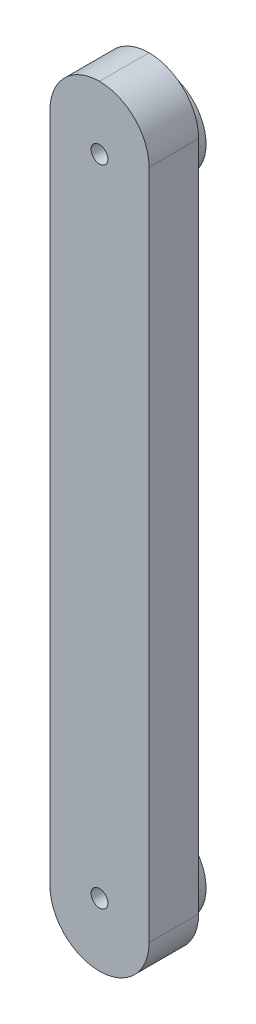
SolidWorks part; units mm, degrees
material "PETG"
ref_plane "Front Plane" through (0, 0, 0) normal (0, 0, 1) x (1, 0, 0)
ref_plane "Top Plane" through (0, 0, 0) normal (0, 1, 0) x (1, 0, 0)
ref_plane "Right Plane" through (0, 0, 0) normal (1, 0, 0) x (0, 0, -1)
sketch "Sketch1" plane through (0, 0, 0) normal (0, 0, 1) x (1, 0, 0)
  line L1 (-10, 77.75) -> (10, 77.75)
  line L2 (-10, 77.75) -> (-10, -77.75)
  line L3 (-10, -77.75) -> (10, -77.75)
  line L4 (10, 77.75) -> (10, -77.75)
  point P8 (-10, 0)
  point P9 (0, 77.75)
  dimension "D1" = 20
  dimension "D2" = 155.5
extrude "Boss-Extrude1" add sketch "Sketch1" along normal blind 10
sketch "Sketch2" plane through (0, 0, 0) normal (0, 0, -1) x (-1, 0, 0)
  line L0 (0, 65) -> (0, -65) construction
  circle A0 centre (0, 65) radius 9
  circle A1 centre (0, -65) radius 9
  dimension "D1" = 130
  dimension "D2" = 18
extrude "Boss-Extrude2" add sketch "Sketch2" along normal blind 2.5
fillet "Fillet1" radius 10 4 edges at (10, -77.75, 5) (-10, -77.75, 5) (-10, 77.75, 5) (10, 77.75, 5)
sketch "Sketch3" plane through (0, 0, -2.5) normal (0, 0, -1) x (-1, 0, 0)
  circle A0 centre (0, 65) radius 1.7
  circle A1 centre (0, -65) radius 1.7
  dimension "D1" = 3.4
extrude "Cut-Extrude1" cut sketch "Sketch3" against normal through all
equation "\"tol_dia_id_intfc\" = 0.0200mm ' For hole diameters - Interference fit"
equation "\"tol_dia_id_slip\"  = 0.0300mm ' For hole diameters - Slip fit"
equation "\"tol_dia_id_clear\" = 0.0500mm ' For hole diameters - Clearance fit"
equation "\"tol_dia_od_intfc\" = 0.0200mm ' For shaft diameters - Interference fit"
equation "\"tol_dia_od_slip\"  = 0.0300mm ' For shaft diameters - Slip fit"
equation "\"tol_dia_od_clear\" = 0.0500mm ' For shaft diameters - Clearance fit"
equation "\"tol_general_intfc\"= 0.0030mm ' For general parts (Horiz) - Interference fit"
equation "\"tol_general_slip\" = 0.0050mm ' For general parts (Horiz) - Slip fit"
equation "\"tol_general_clear\"= 0.0100mm ' For general parts (Horiz) - Clearance fit"
equation "\"tol_layer_intfc\"  = 0.0030mm ' For all parts (Vert) - Interference fit"
equation "\"tol_layer_slip\"   = 0.0050mm ' For all parts (Vert) - Slip fit"
equation "\"tol_layer_clear\"  = 0.0100mm ' For all parts (Vert) - Clearance fit"
equation "\"tol_corner_rad\"   = 0.100mm ' For corners that fit into other parts"
